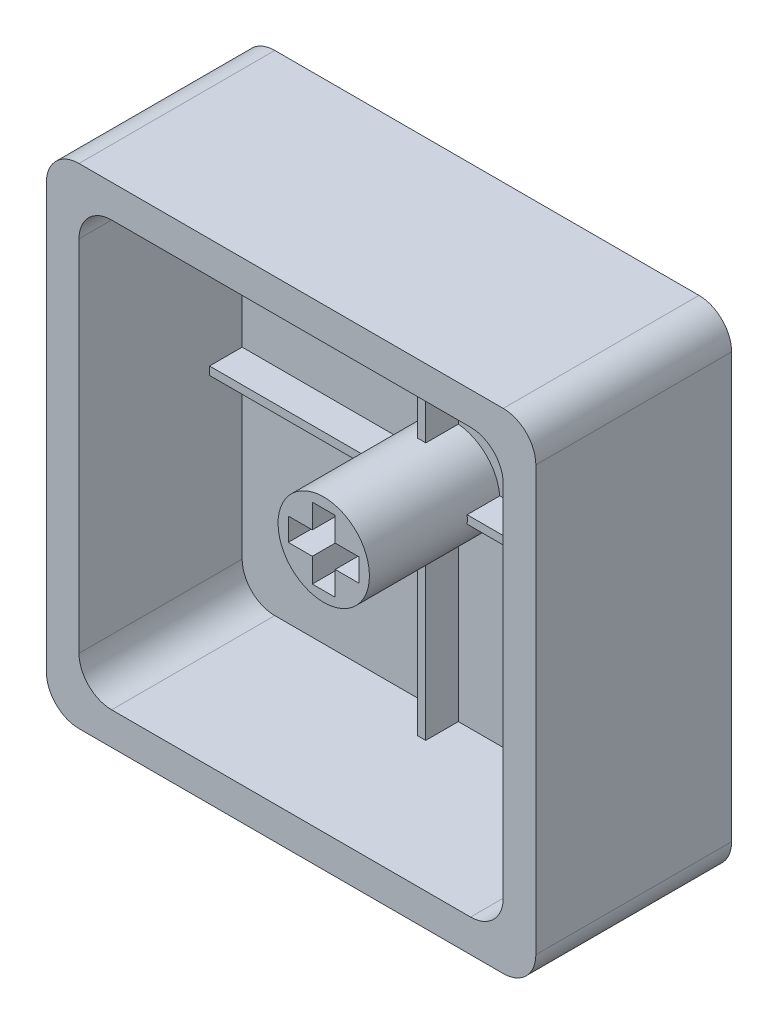
SolidWorks part; units mm, degrees
ref_plane "前视基准面" through (0, 0, 0) normal (0, 0, 1) x (1, 0, 0)
ref_plane "上视基准面" through (0, 0, 0) normal (0, 1, 0) x (1, 0, 0)
ref_plane "右视基准面" through (0, 0, 0) normal (1, 0, 0) x (0, 0, -1)
sketch "草图1" plane through (0, 0, 0) normal (0, 0, 1) x (1, 0, 0)
  line L0 (-13, 15) -> (13, 15)
  line L1 (-11, 13) -> (11, 13)
  line L2 (-13, 11) -> (-13, -11)
  line L3 (-11, -13) -> (11, -13)
  line L4 (13, 11) -> (13, -11)
  line L5 (0, -13) -> (0, 13) construction
  line L6 (-13, 0) -> (13, 0) construction
  line L7 (15, 13) -> (15, -13)
  line L8 (-13, -15) -> (13, -15)
  line L9 (-15, 13) -> (-15, -13)
  line L10 (-13, -13) -> (13, -13) construction
  line L11 (-2.175, 0.7) -> (2.175, 0.7)
  line L12 (-2.175, 0.7) -> (-2.175, -0.7)
  line L13 (-2.175, -0.7) -> (2.175, -0.7)
  line L14 (2.175, 0.7) -> (2.175, -0.7)
  line L15 (0, -0.7) -> (0, 0.7) construction
  line L16 (-2.175, 0) -> (2.175, 0) construction
  line L17 (-0.7, 2.175) -> (0.7, 2.175)
  line L18 (-0.7, 2.175) -> (-0.7, -2.175)
  line L19 (-0.7, -2.175) -> (0.7, -2.175)
  line L20 (0.7, 2.175) -> (0.7, -2.175)
  line L21 (0, -2.175) -> (0, 2.175) construction
  line L22 (-0.7, 0) -> (0.7, 0) construction
  line L23 (13, 13) -> (13, -13) construction
  line L24 (-13, 13) -> (13, 13) construction
  line L25 (-13, 13) -> (-13, -13) construction
  line L26 (-15, 15) -> (-15, -15) construction
  line L27 (-15, -15) -> (15, -15) construction
  line L28 (15, 15) -> (15, -15) construction
  line L29 (-15, 15) -> (15, 15) construction
  line L30 (0.25, 13) -> (0.25, 2.7888)
  line L31 (-13, 0.25) -> (-2.7888, 0.25)
  line L32 (-13, 0.25) -> (-13, -0.25)
  line L33 (-13, -0.25) -> (-2.7888, -0.25)
  line L35 (-7.8944, -0.25) -> (-7.8944, 0.25) construction
  line L36 (-13, 0) -> (-2.5, 0) construction
  line L37 (0.25, 13) -> (-0.25, 13)
  line L39 (-0.25, 13) -> (-0.25, 2.7888)
  line L40 (13, -0.25) -> (2.7888, -0.25)
  line L41 (13, -0.25) -> (13, 0.25)
  line L43 (13, 0.25) -> (2.7888, 0.25)
  line L44 (-0.25, -13) -> (-0.25, -2.7888)
  line L45 (-0.25, -13) -> (0.25, -13)
  line L47 (0.25, -13) -> (0.25, -2.7888)
  circle A0 centre (0, 0) radius 2.8
  arc A1 (11, -13) -> (13, -11) centre (11, -11) ccw
  arc A2 (13, 11) -> (11, 13) centre (11, 11) ccw
  arc A3 (-13, 11) -> (-11, 13) centre (-11, 11) cw
  arc A4 (-13, -11) -> (-11, -13) centre (-11, -11) ccw
  arc A5 (-15, -13) -> (-13, -15) centre (-13, -13) ccw
  arc A6 (13, -15) -> (15, -13) centre (13, -13) ccw
  arc A7 (15, 13) -> (13, 15) centre (13, 13) ccw
  arc A8 (-15, 13) -> (-13, 15) centre (-13, 13) cw
  point P0 (0, 0)
  point P19 (13, -13)
  point P41 (-7.8944, 0)
  point P66 (0, 0)
  dimension "D4" = 5.6
  dimension "D9" = 2
  dimension "D1" = 30
  dimension "D2" = 30
  dimension "D5" = 4.35
  dimension "D6" = 1.4
  dimension "D7" = 4.35
  dimension "D8" = 1.4
  dimension "D10" = 0.5
  dimension "D3" = 2
  dimension "D12" = 4
extrude "凸台-拉伸1" add sketch "草图1" along normal blind 10 contours A8 L9 A5 L8 A6 L7 A7 L0 A4 L2 A3 L1 A2 L4 A1 L3 region at (0, 14.5757, 0)
extrude "凸台-拉伸2" add sketch "草图1<6>" along normal blind 8 separate body contours A0 L17 L20 L11 L14 L13 L19 L18 L12 region at (0, 2.7208, 0)
sketch "草图1<6>" plane through (0, 0, 0) normal (0, 0, 1) x (1, 0, 0) same geometry as "草图1"
extrude "凸台-拉伸3" add sketch "草图1<7>" against normal blind 2 contours L8 A6 L7 A7 L0 A8 L9 A5
sketch "草图1<7>" plane through (0, 0, 0) normal (0, 0, 1) x (1, 0, 0) same geometry as "草图1"
extrude "凸台-拉伸4" add sketch "草图1<9>" along normal blind 2 contours A0 L31 L2 L33 | A0 L30 L1 L39 | A0 L40 L4 L43 | A0 L44 L3 L47 region at (0, 7.8981, 0) region at (-7.8981, 0, 0) region at (7.8981, 0, 0) region at (0, -7.8981, 0)
sketch "草图1<9>" plane through (0, 0, 0) normal (0, 0, 1) x (1, 0, 0) same geometry as "草图1"
